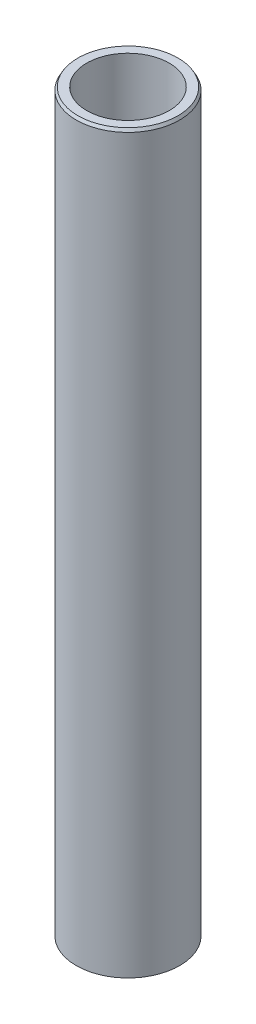
SolidWorks part; units mm, degrees
ref_plane "Front Plane" through (0, 0, 0) normal (0, 0, 1) x (1, 0, 0)
ref_plane "Top Plane" through (0, 0, 0) normal (0, 1, 0) x (1, 0, 0)
ref_plane "Right Plane" through (0, 0, 0) normal (1, 0, 0) x (0, 0, -1)
sketch "Sketch1" plane through (0, 0, 0) normal (0, 1, 0) x (1, 0, 0)
  circle A0 centre (0, 0) radius 20
  dimension "SHAFT_OD" = 40
extrude "Boss-Extrude1" add sketch "Sketch1" along normal blind 284.9775
sketch "Sketch2" plane through (0, 0, 0) normal (0, 1, 0) x (1, 0, 0)
  circle A0 centre (0, 0) radius 15.9463
  dimension "BORE_D" = 31.8926
extrude "Cut-Extrude1" cut sketch "Sketch2" along normal through all
chamfer "Chamfer1" distance 1.1258 angle 30 2 edges at (0, 284.9775, 20) (0, 0, 20) first distance on face at (0, 284.9775, 20) first distance on face at (0, 0, 15.9463)
